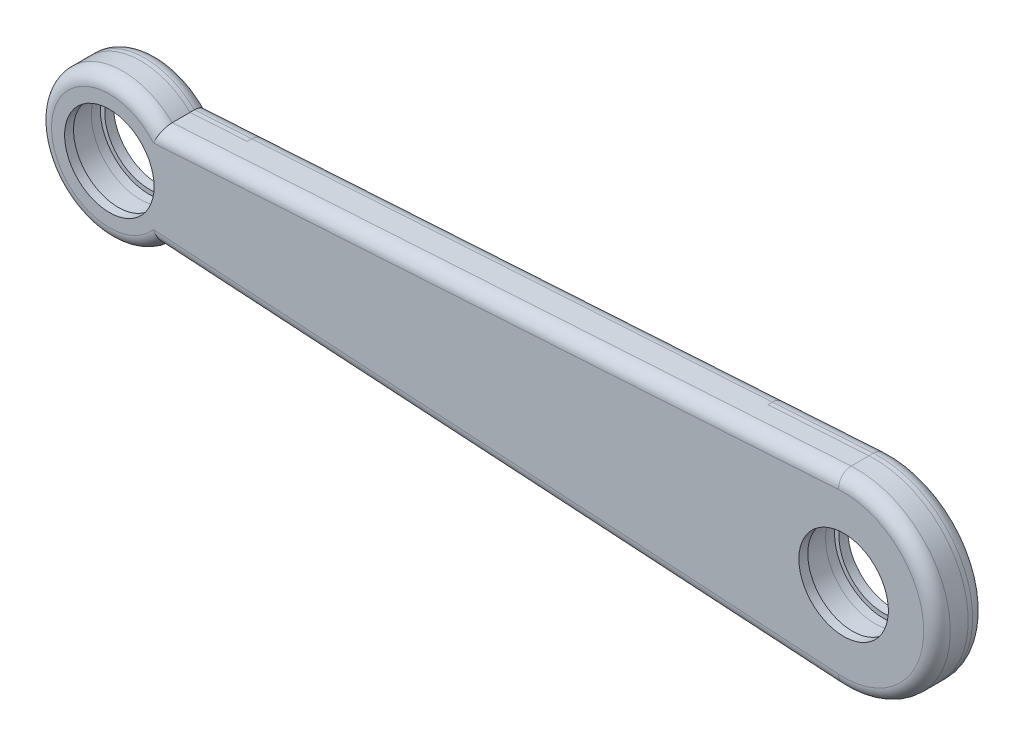
SolidWorks part; units mm, degrees
ref_plane "Front Plane" through (0, 0, 0) normal (0, 0, 1) x (1, 0, 0)
ref_plane "Top Plane" through (0, 0, 0) normal (0, 1, 0) x (1, 0, 0)
ref_plane "Right Plane" through (0, 0, 0) normal (1, 0, 0) x (0, 0, -1)
sketch "Sketch6" plane through (0, 0, 0) normal (0, 0, 1) x (1, 0, 0)
  line L0 (11.1243, -11.5) -> (163.7005, -20.9598)
  line L1 (122.7946, 12.4121) -> (35.5841, 7.005)
  line L2 (11.1243, 11.5) -> (163.7005, 20.9598)
  line L3 (-58.5211, 0) -> (213.089, 0) construction
  line L4 (35.5841, -7.005) -> (122.7946, -12.4121)
  line L8 (0, 0) -> (165, 0) construction
  line L9 (82.5, -26.3413) -> (82.5, 31.169) construction
  line L13 (24, 12.2983) -> (24, -12.2983)
  line L14 (141, 19.5523) -> (141, -19.5523)
  circle A2 centre (165, 0) radius 21 construction
  circle A3 centre (0, 0) radius 11.05
  circle A4 centre (0, 0) radius 16 construction
  circle A8 centre (0, 0) radius 10.05
  arc A9 (11.1243, 11.5) -> (11.1243, -11.5) centre (0, 0) ccw
  arc A10 (163.7005, 20.9598) -> (163.7005, -20.9598) centre (165, 0) cw
  arc A11 (35.5841, 7.005) -> (35.5841, -7.005) centre (36.0184, 0) ccw
  arc A12 (122.7946, -12.4121) -> (122.7946, 12.4121) centre (123.5641, 0) ccw
  circle A14 centre (16, 0) radius 2.2
  circle A15 centre (165, 0) radius 10.05
  circle A16 centre (165, 0) radius 11.05
  circle A17 centre (149, 0) radius 2.2
  point P24 (0, 0)
  point P29 (82.5, 0)
  dimension "D2" = 1
  dimension "D3" = 165
  dimension "D4" = 22.1
  dimension "D5" = 32
  dimension "D6" = 8
  dimension "D7" = 5
  dimension "D8" = 42
  dimension "D9" = 8
  dimension "D10" = 5
  dimension "D11" = 4.4
  dimension "D13" = 6
  dimension "D12" = 23
  dimension "D14" = 6
extrude "Boss-Extrude1" add sketch "Sketch6" along normal blind 11 contours L2 A10 L0 A9
extrude "Cut-Extrude1" cut sketch "Sketch6<20>" along normal offset from surface (7 mm away) 2 from offset 2 contours A3 | A16 up to face at (86.2062, 0, 11)
sketch "Sketch6<20>" plane through (0, 0, 0) normal (0, 0, 1) x (1, 0, 0) same geometry as "Sketch6"
extrude "Cut-Extrude4" cut sketch "Sketch6<23>" along normal through all contours A15 | A8
sketch "Sketch6<23>" plane through (0, 0, 0) normal (0, 0, 1) x (1, 0, 0) same geometry as "Sketch6"
extrude "Cut-Extrude5" cut sketch "Sketch6<24>" along normal offset from surface (8 mm away) 3 contours L4 A12 L1 A11 up to face at (10.05, 0, 11)
sketch "Sketch6<24>" plane through (0, 0, 0) normal (0, 0, 1) x (1, 0, 0) same geometry as "Sketch6"
fillet "Fillet2" radius 3 12 edges at (-16, 0, 11) (87.4124, -16.2299, 11) (186, 0, 11) (87.4124, 16.2299, 11) (136, 0, 0) (79.1893, -9.7085, 0) (29, 0, 0) (79.1893, 9.7085, 0) (-16, 0, 0) (87.4124, 16.2299, 0) (186, 0, 0) (87.4124, -16.2299, 0)
extrude "Cut-Extrude6" cut sketch "Sketch6<27>" along normal blind 6 from offset 4 contours A14 | A17
sketch "Sketch6<27>" plane through (0, 0, 0) normal (0, 0, 1) x (1, 0, 0) same geometry as "Sketch6"
hole_wizard "CSK for M3 Flat Head Machine Screw1" positions "Sketch7" profile "Sketch8" countersink size "M3" standard "ANSI Metric"
sketch "Sketch7" plane through (0, 0, 0) normal (0, 0, -1) x (-1, 0, 0)
  line L1 (-82.5, 31.169) -> (-82.5, -26.3413) construction
  point P0 (-16, 0)
  point P13 (0, 0)
  point P14 (-149, 0)
sketch "Sketch8" plane through (16, 0, 0) normal (1, 0, 0) x (0, 1, 0)
  line L0 (0, 0) -> (0, 5.0215)
  line L1 (0, 5.0215) -> (1.7, 4)
  line L2 (1.7, 4) -> (1.7, 1.45)
  line L3 (1.7, 1.45) -> (3.15, 0)
  line L5 (3.15, 0) -> (0, 0)
  line L6 (-1.7, 1.45) -> (-3.15, 0) construction
  line L10 (0, 5.0215) -> (-1.7, 4) construction
  line L11 (0, -6.35) -> (0, 107.95) construction
  dimension "Hole Dia." = 3.4
  dimension "Hole Depth" = 4
  dimension "Near C'Sink Dia." = 6.3
  dimension "Near C'Sink Angle" = 90
  dimension "Drill Angle" = 118
sketch "Sketch9" plane through (0, 0, 0) normal (0, 1, 0) x (1, 0, 0)
  line L0 (-20.0212, -4) -> (24, -4)
  line L1 (24, -4) -> (24, 0)
  line L2 (0, 0) -> (165, 0) construction
  line L3 (196.9088, -4) -> (141, -4)
  line L4 (141, -4) -> (141, 0)
  line L5 (-58.5211, 0) -> (213.089, 0) construction
  point P7 (0, 0)
  dimension "D1" = 4
split "Split1" trim tools "Sketch9" bodies to split 135 resulting bodies 136 137 138
